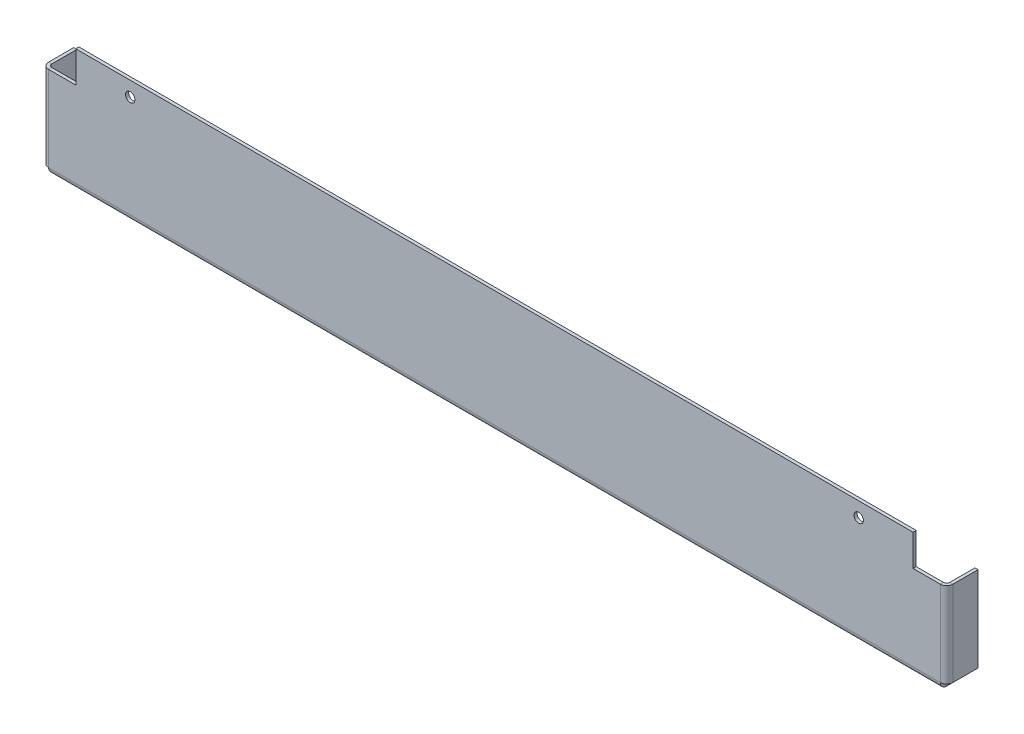
SolidWorks part; units mm, degrees
note: The reader was unsure of these and kept them because the rebuilt part matched: thickness of "Базовая кромка1", "Ребро-кромка2", "Ребро-кромка3", "Ребро-кромка4", "Листовой металл1", "Листовой металл3", "Листовой металл4", "Листовой металл5", "Листовой металл7", "Листовой металл8", "Листовой металл9"; flange length of "Ребро-кромка2", "Ребро-кромка3", "Ребро-кромка4".
material "1060 Сплав"
ref_plane "Front" through (0, 0, 0) normal (0, 0, 1) x (1, 0, 0)
ref_plane "Top" through (0, 0, 0) normal (0, 1, 0) x (1, 0, 0)
ref_plane "Right" through (0, 0, 0) normal (1, 0, 0) x (0, 0, -1)
sketch "Эскиз1" plane through (0, 0, 0) normal (0, 0, 1) x (1, 0, 0)
  line L1 (0, 0) -> (426, 0)
  line L2 (0, 0) -> (0, 55.7)
  line L3 (0, 55.7) -> (426, 55.7)
  line L4 (426, 0) -> (426, 55.7)
  dimension "D1" = 55.7
  dimension "D2" = 426
base flange "Базовая кромка1" sketch "Эскиз1" thickness 1.5 reverse thickness direction no parameters "D1"=2
edge flange "Ребро-кромка2" sketch "Эскиз18" flange angle 90 flange length 15 flange position bend outside bend radius 1.5 thickness 1.5 relief rectangular parameters "D6"=10, "D8"=1
sketch "Эскиз18" plane through (0, 0, -1.5) normal (-1, 0, 0) x (0, 1, 0)
  line L0 (55.7, 0) -> (0, 0) construction
  line L1 (55.7, 0) -> (0, 0)
  line L2 (0, 0) -> (0, 13.5)
  line L3 (0, 13.5) -> (55.7, 13.5)
  line L4 (55.7, 13.5) -> (55.7, 0)
bend "EdgeBend4" bend radius 1.5 bend angle 90 parameters "D5"=4
edge flange "Ребро-кромка3" sketch "Эскиз21" flange angle 90 flange length 15 flange position bend outside bend radius 1.5 thickness 1.5 relief rectangular parameters "D6"=10
sketch "Эскиз21" plane through (0, 0, -1.5) normal (0, -1, 0) x (-1, 0, 0)
  line L2 (-426, 0) -> (-426, 13.5)
  line L3 (-426, 13.5) -> (0, 13.5)
  line L4 (0, 13.5) -> (0, 0)
  line L7 (0, 0) -> (-426, 0) construction
  line L8 (0, 0) -> (-426, 0)
bend "EdgeBend5" bend radius 1.5 bend angle 90 parameters "D5"=5
edge flange "Ребро-кромка4" sketch "Эскиз24" flange angle 90 flange length 15 flange position bend outside bend radius 1.5 thickness 1.5 relief rectangular parameters "D6"=10
sketch "Эскиз24" plane through (426, 0, -1.5) normal (1, 0, 0) x (0, -1, 0)
  line L0 (0, 0) -> (-55.7, 0) construction
  line L1 (0, 0) -> (-55.7, 0)
  line L2 (-55.7, 0) -> (-55.7, 13.5)
  line L3 (-55.7, 13.5) -> (0, 13.5)
  line L4 (0, 13.5) -> (0, 0)
bend "EdgeBend6" bend radius 1.5 bend angle 90 parameters "D5"=6
sketch "Эскиз25" plane through (-3, 0, 0) normal (-1, 0, 0) x (0, 0, 1)
  line L1 (-15, 55.7) -> (0, 55.7)
  line L2 (-15, 55.7) -> (-15, 40.7)
  line L3 (-15, 40.7) -> (0, 40.7)
  line L4 (0, 55.7) -> (0, 40.7)
  dimension "D1" = 15
  dimension "D2" = 15
extrude "Вырез-Вытянуть1" cut sketch "Эскиз25" against normal blind 16 normal cut yes
sketch "Эскиз26" plane through (429, 0, 0) normal (1, 0, 0) x (0, 0, -1)
  line L1 (15, 55.7) -> (0, 55.7)
  line L2 (15, 55.7) -> (15, 40.7)
  line L3 (15, 40.7) -> (0, 40.7)
  line L4 (0, 55.7) -> (0, 40.7)
  dimension "D1" = 15
extrude "Вырез-Вытянуть2" cut sketch "Эскиз26" against normal blind 16 normal cut yes
sketch "Эскиз27" plane through (0, 0, 0) normal (0, 0, 1) x (1, 0, 0)
  line L0 (0, 55.7) -> (426, 55.7) construction
  line L1 (-3, 40.7) -> (-3, 0) construction
  line L2 (429, 0) -> (429, 40.7) construction
  circle A0 centre (39, 48.7) radius 2.25
  circle A1 centre (387, 48.7) radius 2.25
  dimension "D1" = 4.5
  dimension "D2" = 4.5
  dimension "D3" = 7
  dimension "D4" = 7
  dimension "D5" = 42
  dimension "D6" = 42
extrude "Вырез-Вытянуть3" cut sketch "Эскиз27" against normal through all normal cut yes
sketch "Сгиб-Линии1" [suppressed] plane through (0, 0, 0) normal (0, 1, 0) x (1, 0, 0)
sketch "Граничная рамка1" [suppressed] plane through (0, 0, 0) normal (0, 1, 0) x (1, 0, 0)
sheet metal parameters "Листовой металл1" thickness 1.5 parameters "D1"=2
flat pattern "Развертка1" [suppressed]
sketch "Сгиб-Линии2" plane through (0, 0, 0) normal (0, 1, 0) x (1, 0, 0)
sketch3d "Граничная рамка2" [suppressed]
  line L0 (0, 0, 0) -> (-432, 0, 0) construction
  line L1 (0, 43.7, 0) -> (-432, 43.7, 0) construction
  line L2 (0, 0, 0) -> (0, 43.7, 0) construction
  line L3 (-432, 0, 0) -> (-432, 43.7, 0) construction
sheet metal parameters "Листовой металл3" thickness 1.5 parameters "D1"=2, "D7"=2
flat pattern "Развертка1"
sketch "Сгиб-Линии2" plane through (0, 0, 0) normal (0, 0, 1) x (1, 0, 0)
  line L0 (432, 46.0562) -> (0, 46.0562) construction
  line L1 (432, 46.0562) -> (0, 46.0562) construction
  line L2 (-2.3562, 43.7) -> (-2.3562, 0) construction
  line L5 (-2.3562, 43.7) -> (-2.3562, 0) construction
sketch3d "Граничная рамка2" [suppressed]
  line L0 (-15.7124, 0, 0) -> (432, 0, 0) construction
  line L1 (-15.7124, 88.4124, 0) -> (432, 88.4124, 0) construction
  line L2 (-15.7124, 0, 0) -> (-15.7124, 88.4124, 0) construction
  line L3 (432, 0, 0) -> (432, 88.4124, 0) construction
bend of the flat pattern "Плоское состояние-<EdgeBend4>1"
sheet metal parameters "Листовой металл4" thickness 1.5 parameters "D1"=2, "D7"=2
flat pattern "Развертка1"
sketch "Сгиб-Линии2" plane through (0, 0, 0) normal (0, 0, 1) x (1, 0, 0)
  line L0 (432, 46.0562) -> (0, 46.0562) construction
  line L1 (432, 46.0562) -> (0, 46.0562) construction
  line L2 (-2.3562, 43.7) -> (-2.3562, 0) construction
  line L3 (0, -2.3562) -> (432, -2.3562) construction
  line L4 (0, -2.3562) -> (432, -2.3562) construction
  line L5 (-2.3562, 43.7) -> (-2.3562, 0) construction
sketch3d "Граничная рамка2" [suppressed]
  line L0 (-15.7124, -15.7124, 0) -> (432, -15.7124, 0) construction
  line L1 (-15.7124, 88.4124, 0) -> (432, 88.4124, 0) construction
  line L2 (-15.7124, -15.7124, 0) -> (-15.7124, 88.4124, 0) construction
  line L3 (432, -15.7124, 0) -> (432, 88.4124, 0) construction
bend of the flat pattern "Плоское состояние-<EdgeBend4>1"
bend of the flat pattern "Плоское состояние-<EdgeBend5>1"
sheet metal parameters "Листовой металл5" thickness 1.5 parameters "D1"=2, "D7"=2
flat pattern "Развертка1"
sketch "Сгиб-Линии2" plane through (0, 0, 0) normal (0, 0, 1) x (1, 0, 0)
  line L2 (-1.7671, 56.7) -> (-1.7671, 0) construction
  line L3 (0, -1.7671) -> (426, -1.7671) construction
  line L4 (0, -1.7671) -> (426, -1.7671) construction
  line L5 (-1.7671, 56.7) -> (-1.7671, 0) construction
  line L6 (427.7671, 0) -> (427.7671, 56.7) construction
  line L7 (427.7671, 0) -> (427.7671, 56.7) construction
sketch3d "Граничная рамка2" [suppressed]
  line L0 (-15.5343, -15.5343, 0) -> (441.5343, -15.5343, 0) construction
  line L1 (-15.5343, 56.7, 0) -> (441.5343, 56.7, 0) construction
  line L2 (-15.5343, -15.5343, 0) -> (-15.5343, 56.7, 0) construction
  line L3 (441.5343, -15.5343, 0) -> (441.5343, 56.7, 0) construction
bend of the flat pattern "Плоское состояние-<EdgeBend4>1"
bend of the flat pattern "Плоское состояние-<EdgeBend5>1"
bend of the flat pattern "Плоское состояние-<EdgeBend6>1"
sheet metal parameters "Листовой металл7" thickness 1.5 parameters "D1"=2, "D7"=2
flat pattern "Развертка1"
sketch "Сгиб-Линии2" plane through (0, 0, 0) normal (0, 0, 1) x (1, 0, 0)
  line L2 (-1.7671, 39.7) -> (-1.7671, 0) construction
  line L3 (0, -1.7671) -> (426, -1.7671) construction
  line L4 (0, -1.7671) -> (426, -1.7671) construction
  line L5 (-1.7671, 39.7) -> (-1.7671, 0) construction
  line L6 (427.7671, 0) -> (427.7671, 56.7) construction
  line L7 (427.7671, 0) -> (427.7671, 56.7) construction
sketch3d "Граничная рамка2" [suppressed]
  line L0 (-15.5343, -15.5343, 0) -> (441.5343, -15.5343, 0) construction
  line L1 (-15.5343, 56.7, 0) -> (441.5343, 56.7, 0) construction
  line L2 (-15.5343, -15.5343, 0) -> (-15.5343, 56.7, 0) construction
  line L3 (441.5343, -15.5343, 0) -> (441.5343, 56.7, 0) construction
bend of the flat pattern "Плоское состояние-<EdgeBend4>1"
bend of the flat pattern "Плоское состояние-<EdgeBend5>1"
bend of the flat pattern "Плоское состояние-<EdgeBend6>1"
sheet metal parameters "Листовой металл8" thickness 1.5 parameters "D1"=2, "D7"=2
flat pattern "Развертка1"
sketch "Сгиб-Линии2" plane through (0, 0, 0) normal (0, 0, 1) x (1, 0, 0)
  line L2 (-1.7671, 40.7) -> (-1.7671, 0) construction
  line L3 (0, -1.7671) -> (426, -1.7671) construction
  line L4 (0, -1.7671) -> (426, -1.7671) construction
  line L5 (-1.7671, 40.7) -> (-1.7671, 0) construction
  line L6 (427.7671, 0) -> (427.7671, 40.7) construction
  line L7 (427.7671, 0) -> (427.7671, 40.7) construction
sketch3d "Граничная рамка2" [suppressed]
  line L0 (-15.5343, -15.5343, 0) -> (441.5343, -15.5343, 0) construction
  line L1 (-15.5343, 55.7, 0) -> (441.5343, 55.7, 0) construction
  line L2 (-15.5343, -15.5343, 0) -> (-15.5343, 55.7, 0) construction
  line L3 (441.5343, -15.5343, 0) -> (441.5343, 55.7, 0) construction
bend of the flat pattern "Плоское состояние-<EdgeBend4>1"
bend of the flat pattern "Плоское состояние-<EdgeBend5>1"
bend of the flat pattern "Плоское состояние-<EdgeBend6>1"
sheet metal parameters "Листовой металл9" thickness 1.5 parameters "D1"=2, "D7"=2
flat pattern "Развертка1"
sketch "Сгиб-Линии2" plane through (0, 0, 0) normal (0, 0, 1) x (1, 0, 0)
  line L2 (-1.7671, 40.7) -> (-1.7671, 0) construction
  line L3 (0, -1.7671) -> (426, -1.7671) construction
  line L4 (0, -1.7671) -> (426, -1.7671) construction
  line L5 (-1.7671, 40.7) -> (-1.7671, 0) construction
  line L6 (427.7671, 0) -> (427.7671, 40.7) construction
  line L7 (427.7671, 0) -> (427.7671, 40.7) construction
sketch3d "Граничная рамка2" [suppressed]
  line L0 (-15.5343, -15.5343, 0) -> (441.5343, -15.5343, 0) construction
  line L1 (-15.5343, 55.7, 0) -> (441.5343, 55.7, 0) construction
  line L2 (-15.5343, -15.5343, 0) -> (-15.5343, 55.7, 0) construction
  line L3 (441.5343, -15.5343, 0) -> (441.5343, 55.7, 0) construction
bend of the flat pattern "Плоское состояние-<EdgeBend4>1"
bend of the flat pattern "Плоское состояние-<EdgeBend5>1"
bend of the flat pattern "Плоское состояние-<EdgeBend6>1"
